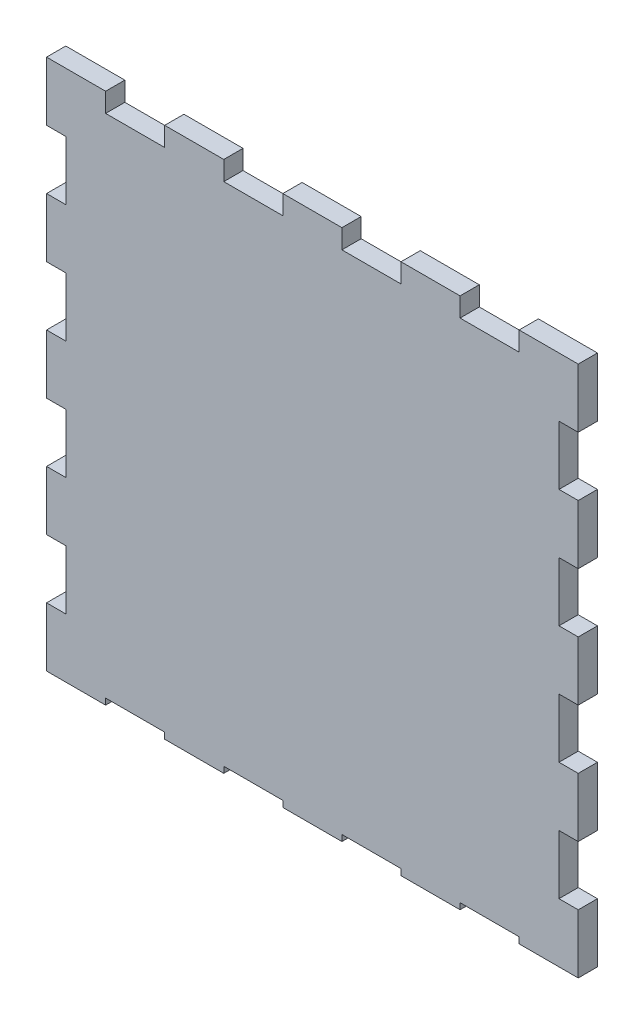
SolidWorks part; units mm, degrees
ref_plane "Front Plane" through (0, 0, 0) normal (0, 0, 1) x (1, 0, 0)
ref_plane "Top Plane" through (0, 0, 0) normal (0, 1, 0) x (1, 0, 0)
ref_plane "Right Plane" through (0, 0, 0) normal (1, 0, 0) x (0, 0, -1)
sketch "Sketch2" plane through (0, 0, 0) normal (0, 0, 1) x (1, 0, 0)
  line L0 (-68.58, -68.58) -> (68.58, 68.58) construction
  line L1 (-68.58, -68.58) -> (68.58, -68.58)
  line L2 (-68.58, -68.58) -> (-68.58, 68.58)
  line L3 (-68.58, 68.58) -> (68.58, 68.58)
  line L4 (68.58, -68.58) -> (68.58, 68.58)
  line L5 (68.58, -68.58) -> (-68.58, 68.58) construction
  point P0 (23.0915, 23.0915)
  dimension "D2" = 137.16
  dimension "D3" = 137.16
extrude "Boss-Extrude1" add sketch "Sketch2" along normal blind 4.9609
sketch "Sketch3" plane through (0, 0, 4.9609) normal (0, 0, 1) x (1, 0, 0)
  line L20 (-68.58, 68.58) -> (-68.58, 53.34) construction
  line L21 (-68.58, -68.58) -> (68.58, -68.58) construction
  line L22 (-68.58, 22.86) -> (-68.58, 7.62)
  line L23 (-68.58, 53.34) -> (-63.619, 53.34)
  line L24 (-68.58, 53.34) -> (-68.58, 38.1)
  line L25 (-68.58, 38.1) -> (-63.619, 38.1)
  line L26 (-63.619, 53.34) -> (-63.619, 38.1)
  line L27 (-68.58, 22.86) -> (-63.619, 22.86)
  line L28 (-63.619, 22.86) -> (-63.619, 7.62)
  line L29 (-68.58, 7.62) -> (-63.619, 7.62)
  line L30 (-68.58, -7.62) -> (-68.58, -22.86)
  line L31 (-68.58, -7.62) -> (-63.619, -7.62)
  line L32 (-63.619, -7.62) -> (-63.619, -22.86)
  line L33 (-68.58, -22.86) -> (-63.619, -22.86)
  line L34 (-68.58, -38.1) -> (-68.58, -53.34)
  line L35 (-68.58, -38.1) -> (-63.619, -38.1)
  line L36 (-63.619, -38.1) -> (-63.619, -53.34)
  line L37 (-68.58, -53.34) -> (-63.619, -53.34)
  line L38 (-68.58, 68.58) -> (-53.34, 68.58) construction
  line L39 (-63.619, 38.1) -> (-63.619, 22.86) construction
  line L60 (-68.58, 68.58) -> (-68.58, -68.58) construction
  line L61 (68.58, 68.58) -> (68.58, 53.34) construction
  line L62 (68.58, 68.58) -> (-68.58, 68.58) construction
  line L63 (68.58, 22.86) -> (68.58, 7.62)
  line L64 (68.58, 53.34) -> (63.619, 53.34)
  line L65 (68.58, 53.34) -> (68.58, 38.1)
  line L66 (68.58, 38.1) -> (63.619, 38.1)
  line L67 (63.619, 53.34) -> (63.619, 38.1)
  line L68 (68.58, 22.86) -> (63.619, 22.86)
  line L69 (63.619, 22.86) -> (63.619, 7.62)
  line L70 (68.58, 7.62) -> (63.619, 7.62)
  line L71 (68.58, -7.62) -> (68.58, -22.86)
  line L72 (68.58, -7.62) -> (63.619, -7.62)
  line L73 (63.619, -7.62) -> (63.619, -22.86)
  line L74 (68.58, -22.86) -> (63.619, -22.86)
  line L75 (68.58, -38.1) -> (68.58, -53.34)
  line L76 (68.58, -38.1) -> (63.619, -38.1)
  line L77 (63.619, -38.1) -> (63.619, -53.34)
  line L78 (68.58, -53.34) -> (63.619, -53.34)
  line L79 (63.619, 38.1) -> (63.619, 22.86) construction
  line L80 (-22.86, 68.58) -> (-22.86, 63.619)
  line L81 (-53.34, 68.58) -> (-38.1, 68.58)
  line L82 (-53.34, 68.58) -> (-53.34, 63.619)
  line L83 (-53.34, 63.619) -> (-38.1, 63.619)
  line L84 (-38.1, 68.58) -> (-38.1, 63.619)
  line L85 (-22.86, 68.58) -> (-7.62, 68.58)
  line L86 (-7.62, 68.58) -> (-7.62, 63.619)
  line L87 (-22.86, 63.619) -> (-7.62, 63.619)
  line L88 (7.62, 68.58) -> (7.62, 63.619)
  line L89 (7.62, 68.58) -> (22.86, 68.58)
  line L90 (22.86, 68.58) -> (22.86, 63.619)
  line L91 (7.62, 63.619) -> (22.86, 63.619)
  line L92 (38.1, 68.58) -> (38.1, 63.619)
  line L93 (38.1, 68.58) -> (53.34, 68.58)
  line L94 (53.34, 68.58) -> (53.34, 63.619)
  line L95 (38.1, 63.619) -> (53.34, 63.619)
  line L96 (-38.1, 68.58) -> (-22.86, 68.58) construction
  line L97 (-68.58, -68.58) -> (-53.34, -68.58) construction
  line L98 (-38.1, 63.619) -> (-22.86, 63.619) construction
  line L99 (-22.86, -68.58) -> (-22.86, -66.9925)
  line L100 (-53.34, -68.58) -> (-38.1, -68.58)
  line L101 (-53.34, -68.58) -> (-53.34, -66.9925)
  line L102 (-53.34, -66.9925) -> (-38.1, -66.9925)
  line L103 (-38.1, -68.58) -> (-38.1, -66.9925)
  line L104 (-22.86, -68.58) -> (-7.62, -68.58)
  line L105 (-7.62, -68.58) -> (-7.62, -66.9925)
  line L106 (-22.86, -66.9925) -> (-7.62, -66.9925)
  line L107 (7.62, -68.58) -> (7.62, -66.9925)
  line L108 (7.62, -68.58) -> (22.86, -68.58)
  line L109 (22.86, -68.58) -> (22.86, -66.9925)
  line L110 (7.62, -66.9925) -> (22.86, -66.9925)
  line L111 (38.1, -68.58) -> (38.1, -66.9925)
  line L112 (38.1, -68.58) -> (53.34, -68.58)
  line L113 (53.34, -68.58) -> (53.34, -66.9925)
  line L114 (38.1, -66.9925) -> (53.34, -66.9925)
  line L115 (-38.1, -66.9925) -> (-22.86, -66.9925) construction
  dimension "D2" = 15.24
  dimension "D4" = 15.24
  dimension "D10" = 4
  dimension "D13" = 15.24
  dimension "D14" = 1.5875
  dimension "D15" = 15.24
  dimension "D18" = 15.24
  dimension "D3" = 4.961
  dimension "D12" = 15.24
  dimension "D7" = 4
  dimension "D17" = 4
  dimension "D20" = 4
extrude "Cut-Extrude1" cut sketch "Sketch3" against normal through all
